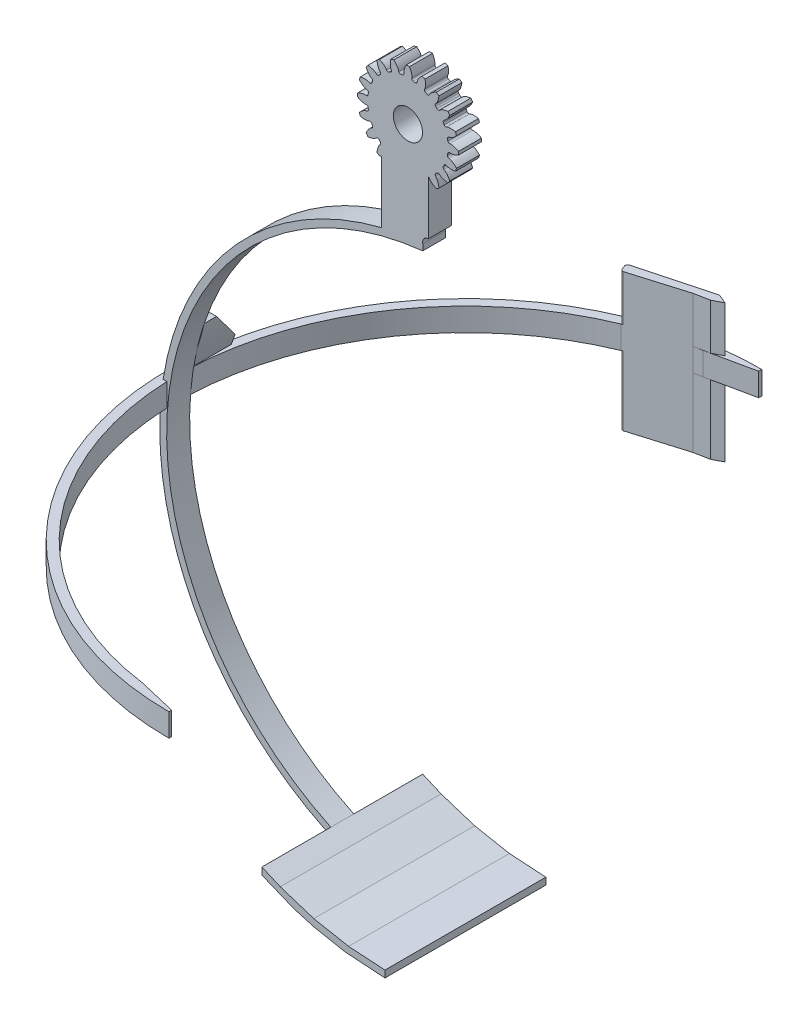
SolidWorks part; units mm, degrees
ref_plane "前视基准面" through (0, 0, 0) normal (0, 0, 1) x (1, 0, 0)
ref_plane "上视基准面" through (0, 0, 0) normal (0, 1, 0) x (1, 0, 0)
ref_plane "右视基准面" through (0, 0, 0) normal (1, 0, 0) x (0, 0, -1)
other "Configuration Table"
ref_axis "Axis1" through (0, 0, -88.99) along (0, 0, 1)
sketch "草图1" plane through (0, 0, 0) normal (0, 0, 1) x (1, 0, 0)
  circle A0 centre (0, 0) radius 22
extrude "LaShenA" add sketch "草图1" along normal blind 10
sketch "SketchA" plane through (0, 0, 10) normal (0, 0, 1) x (1, 0, 0)
  line L0 (0, 0) -> (0, 22) construction
  circle A4 centre (0, 0) radius 18.7939 construction
  circle A5 centre (0, 0) radius 22 construction
  circle A6 centre (0, 0) radius 17.5 construction
  circle A7 centre (0, 0) radius 20 construction
  arc A8 (7.1036, 21.9249) -> (0.0193, 23.0469) centre (0, 0) ccw
  arc A9 (3.9948, 17.8031) -> (3.1175, 17.2201) centre (3.2529, 17.9679) cw
  arc A10 (3.1175, 17.2201) -> (2.3563, 17.3406) centre (0, 0) ccw
  arc A11 (2.3563, 17.3406) -> (1.7022, 18.1662) centre (2.4587, 18.0937) cw
  spline S2 degree 3 poles (3.9948, 17.8031) (4.0347, 17.9825) (4.0765, 18.2192) (4.1572, 18.474) (4.1991, 18.5804) (4.2344, 18.6643) (4.2779, 18.76) (4.33, 18.867) (4.3916, 18.985) (4.4632, 19.1135) (4.5453, 19.252) (4.6387, 19.4001) (4.7439, 19.5573) (4.8615, 19.723) (4.9919, 19.8965) (5.1357, 20.0775) (5.2935, 20.2651) (5.4655, 20.4589) (5.6524, 20.6581) (5.8546, 20.8621) (6.0723, 21.0702) (6.306, 21.2817) (6.6465, 21.5732) (6.9163, 21.7854) (7.1036, 21.9249) knots 0.125068 0.125068 0.125068 0.125068 0.215847 0.244833 0.257593 0.272674 0.290074 0.309794 0.331834 0.356194 0.382875 0.411875 0.443195 0.476835 0.512796 0.551076 0.591676 0.634597 0.679837 0.727398 0.777278 0.829478 0.883999 1 1 1 1
  spline S3 degree 3 poles (1.7022, 18.1662) (1.7197, 18.3492) (1.753, 18.5872) (1.755, 18.8544) (1.7481, 18.9686) (1.7404, 19.0593) (1.7286, 19.1637) (1.7121, 19.2816) (1.69, 19.4129) (1.6617, 19.5572) (1.6263, 19.7144) (1.5833, 19.8841) (1.5318, 20.0661) (1.4712, 20.2599) (1.4008, 20.4653) (1.3199, 20.6818) (1.2279, 20.9091) (1.1241, 21.1465) (1.0079, 21.3937) (0.8787, 21.6502) (0.736, 21.9154) (0.579, 22.1887) (0.3453, 22.5712) (0.1542, 22.8564) (0.0193, 23.0469) knots 0.125068 0.125068 0.125068 0.125068 0.215847 0.244833 0.257593 0.272674 0.290074 0.309794 0.331834 0.356194 0.382875 0.411875 0.443195 0.476835 0.512796 0.551076 0.591676 0.634597 0.679837 0.727398 0.777278 0.829478 0.883999 1 1 1 1
  point P113 (0, 0)
  dimension "Db" = 37.5877
  dimension "Da" = 44
  dimension "Df" = 35
  dimension "Dn" = 40
  dimension "D2" = 2
extrude "Cut-ExtrudeA" cut sketch "SketchA" against normal blind 10
pattern_circular "www.KYTool.cn" count 20 over 360 about axis through (0, 0, -88.99) along (0, 0, 1) of "Cut-ExtrudeA"
ref_plane "基准面1" through (0, 0, 10) normal (0, 0, 1) x (1, 0, 0)
sketch "草图3" plane through (0, 0, 10) normal (0, 0, 1) x (1, 0, 0)
  circle A0 centre (0, 0) radius 6.35
  dimension "D1" = 12.7
extrude "切除-拉伸1" cut sketch "草图3" against normal up to next
sketch "草图4" plane through (0, 0, 10) normal (0, 0, 1) x (1, 0, 0)
  line L0 (0, 0) -> (0, -23.6908) construction
  line L1 (0, 0) -> (34.9845, 0) construction
  line L2 (20, 9.2558) -> (20, -13.0135) construction
  line L7 (20, -40.8194) -> (20, -43.8194)
  line L8 (20, -293.8194) -> (20, -296.8194)
  line L9 (20, -168.8194) -> (20, -43.8194)
  line L10 (20, -168.8194) -> (0, 0) construction
  line L13 (-11.473, -14.7491) -> (-11.473, -44.7491)
  line L14 (8.8831, -41.3031) -> (8.8831, -14.7491)
  line L15 (8.8831, -14.7491) -> (-11.473, -14.7491)
  arc A0 (20, -43.8194) -> (20, -293.8194) centre (20, -168.8194) ccw
  arc A3 (20, -40.8194) -> (8.8831, -41.3031) centre (20, -168.8194) ccw
  arc A4 (-11.473, -44.7491) -> (20, -296.8194) centre (20, -168.8194) ccw
  dimension "D2" = 250
  dimension "D3" = 256
  dimension "D1" = 20
  dimension "D4" = 170
  dimension "D5" = 30
  dimension "D6" = 20.3561
  dimension "D7" = 11.473
extrude "凸台-拉伸7" add sketch "草图4" against normal blind 10 contours L13 A4 L8 A0 L7 A3 L14 L15 region at (16.9025, -42.3194, 10)
sketch "草图5" plane through (0, 0, 10) normal (0, 0, 1) x (1, 0, 0)
  line L0 (-105, -154.4791) -> (20, -154.4791) construction
  line L1 (-107.361, -153.4791) -> (-107.361, -155.4791)
  line L2 (-107.361, -155.4791) -> (-105.8398, -155.4791)
  line L3 (-105.8398, -155.4791) -> (-105.8398, -153.4791)
  line L4 (-105.8398, -153.4791) -> (-107.361, -153.4791)
  dimension "D1" = 1
extrude "凸台-拉伸8" add sketch "草图5" along normal blind 1
ref_plane "基准面2" through (0, -154.4791, 0) normal (0, -1, 0) x (-1, 0, 0)
sketch "草图6" plane through (0, -154.4791, 0) normal (0, -1, 0) x (-1, 0, 0)
  line L0 (-20, -4.2865) -> (-20, 34.8821) construction
  line L1 (108, -5) -> (-41.683, -5) construction
  line L4 (-20, 124) -> (-20, 120)
  line L5 (-20, -130) -> (-20, -134)
  arc A1 (-20, -130) -> (-20, 120) centre (-20, -5) ccw
  arc A2 (-20, -134) -> (-20, 124) centre (-20, -5) ccw
  dimension "D1" = 250
  dimension "D2" = 258
extrude "凸台-拉伸9" add sketch "草图6" along normal blind 5 and the other way blind 5
sketch "草图7" plane through (0, -154.4791, 0) normal (0, -1, 0) x (-1, 0, 0)
  line L0 (-1.8665, -128.5231) -> (-20, -132.8264)
  line L2 (-20, -130) -> (-20, -134) construction
  line L3 (-20, -132.8264) -> (-20, -128.9322)
  line L4 (-20, -128.9322) -> (-1.8665, -128.5231)
extrude "切除-拉伸2" cut sketch "草图7" against normal up to next and the other way up to next contours L4 L3 L0 region at (13.9555, -154.4791, 130.0939)
sketch "草图8" plane through (0, -154.4791, 0) normal (0, -1, 0) x (-1, 0, 0)
  line L0 (-20, 122.6613) -> (0, 118.3896)
  line L1 (-20, 124) -> (-20, 120) construction
  line L2 (-20, 122.6613) -> (-20, 116.0502)
  line L3 (-20, 116.0502) -> (0, 118.3896)
  arc A0 (104.9, 0) -> (-20, 120) centre (-20, -5) ccw construction
extrude "切除-拉伸3" cut sketch "草图8" against normal up to next and the other way up to next
sketch "草图9" plane through (0, 0, 10) normal (0, 0, 1) x (1, 0, 0)
  line L0 (-4.2763, -291.4394) -> (20, -281.4909)
  line L1 (20, -293.8194) -> (20, -296.8194) construction
  line L2 (20, -281.4909) -> (20, -278.1298)
  line L3 (20, -278.1298) -> (-4.2763, -291.4394)
  arc A0 (20, -43.8194) -> (20, -293.8194) centre (20, -168.8194) ccw construction
sketch "草图10" plane through (0, -159.4791, 0) normal (0, -1, 0) x (1, 0, 0)
  line L0 (-3.6833, -117.7359) -> (2.7641, -118.98)
  line L1 (0, -118.3896) -> (20, -122.6613) construction
  line L2 (2.7641, -118.98) -> (6.8079, -121.1064)
  line L3 (6.8079, -121.1064) -> (2.7641, -122.8434)
  line L4 (2.7641, -122.8434) -> (-29.3266, -114.1968)
  line L5 (-29.3266, -114.1968) -> (-27.7971, -110.5008)
  line L6 (-27.7971, -110.5008) -> (-3.6833, -117.7359)
  arc A0 (-104.9, 0) -> (0, -118.3896) centre (20, 5) ccw construction
  arc A1 (20, 134) -> (20, -124) centre (20, 5) ccw construction
extrude "凸台-拉伸10" add sketch "草图10" along normal blind 30 and the other way blind 30
fillet "圆角1" radius 1 2 edges at (-29.3266, -139.4791, -114.1968) (-29.3266, -174.4791, -114.1968)
fillet "圆角2" radius 1 2 edges at (-27.7971, -139.4791, -110.5008) (-27.7971, -174.4791, -110.5008)
ref_plane "基准面3" through (0, -149.4791, 0) normal (0, 1, 0) x (1, 0, 0)
sketch "草图12" plane through (0, -149.4791, 0) normal (0, 1, 0) x (1, 0, 0)
  line L0 (-106.9331, 18) -> (-106.5304, 0)
  line L1 (-106.5304, 0) -> (-90.0177, 0)
  line L2 (-11.473, 0) -> (-106.5304, 0) construction
  line L3 (-90.0177, 0) -> (-90.0177, 18)
  line L4 (-90.0177, 18) -> (-106.9331, 18)
  arc A0 (-29.3266, 114.1968) -> (20, -134) centre (20, -5) ccw construction
  dimension "D1" = 18
extrude "凸台-拉伸11" add sketch "草图12" along normal blind 20
ref_plane "基准面4" through (0, 0, -18) normal (0, 0, -1) x (-1, 0, 0)
ref_plane "基准面5" through (0, 0, 0) normal (0, 0, 1) x (1, 0, 0)
sketch "草图13" plane through (0, 0, 0) normal (0, 0, 1) x (1, 0, 0)
  line L0 (-106.5304, -149.4791) -> (-104.9, -149.4791) construction
  line L1 (-106.5304, -129.4791) -> (-106.5304, -149.4791) construction
  line L2 (-106.5304, -129.4791) -> (-101.8045, -129.4791)
  line L4 (-106.5304, -129.4791) -> (-106.5304, -149.4791)
  line L5 (-98.648, -129.4791) -> (-90.0177, -129.4791)
  line L6 (-98.648, -129.4791) -> (-90.0177, -129.4791) construction
  line L7 (-90.0177, -129.4791) -> (-90.0177, -149.4791)
  line L8 (-90.0177, -149.4791) -> (-104.8955, -149.4791)
  line L9 (20, -149.4791) -> (-109, -149.4791) construction
  line L10 (-103.4948, -149.4791) -> (-90.0177, -149.4791) construction
  arc A1 (-11.473, -44.7491) -> (-106.5304, -149.4791) centre (20, -168.8194) ccw construction
  arc A3 (-98.648, -129.4791) -> (-103.4948, -149.4791) centre (20, -168.8194) ccw construction
  spline S0 degree 3 poles (-101.8045, -129.4791) (-103.9119, -136.0022) (-105.4948, -142.7024) (-106.5304, -149.4791) knots 0 0 0 0 1 1 1 1
  spline S1 degree 2 poles (-98.648, -129.4791) (-101.1177, -139.686) (-104.8955, -149.4791) knots 0 0 0 1 1 1
extrude "切除-拉伸5" cut sketch "草图13" against normal blind 20
ref_plane "基准面6" through (-109, 0, 0) normal (-1, 0, 0) x (0, 0, 1)
sketch "草图14" plane through (-109, 0, 0) normal (-1, 0, 0) x (0, 0, 1)
  line L0 (-5.3466, -129.4791) -> (-18, -144.9052)
  line L1 (-18, -129.4791) -> (0, -129.4791) construction
  line L2 (-18, -129.4791) -> (-18, -149.4791) construction
  line L3 (-18, -144.9052) -> (-18, -129.4791)
  line L4 (-18, -129.4791) -> (-5.3466, -129.4791)
extrude "切除-拉伸6" cut sketch "草图14" against normal blind 20
ref_plane "基准面7" through (0, 0, 10) normal (0, 0, 1) x (1, 0, 0)
ref_plane "基准面9" through (25, 0, 0) normal (1, 0, 0) x (0, 0, -1)
sketch "草图16" plane through (0, 0, 10) normal (0, 0, 1) x (1, 0, 0)
  line L0 (-33.5598, -281.7634) -> (-33.5598, -284.812)
  line L1 (-33.5598, -284.812) -> (-19.5663, -290.5507)
  line L2 (-19.5663, -290.5507) -> (-10.7341, -293.0749)
  line L3 (-10.7341, -293.0749) -> (2.7998, -295.6585)
  line L4 (2.7998, -295.6585) -> (20, -296.8194)
  line L5 (20, -296.8194) -> (20, -293.8194)
  line L6 (20, -293.8194) -> (4.1573, -292.8114)
  line L7 (4.1573, -292.8114) -> (-10.9473, -289.9279)
  line L8 (-10.9473, -289.9279) -> (-25.5548, -285.2229)
  line L9 (-25.5548, -285.2229) -> (-33.5598, -281.7634)
  arc A0 (20, -43.8194) -> (20, -293.8194) centre (20, -168.8194) ccw construction
  arc A1 (-107.6588, -159.4791) -> (20, -296.8194) centre (20, -168.8194) ccw construction
extrude "凸台-拉伸12" add sketch "草图16" along normal blind 30 and the other way blind 40
sketch "草图17" plane through (0, 0, 10) normal (0, 0, 1) x (1, 0, 0)
  circle A0 centre (8.8831, -41.3031) radius 2.5
  dimension "D1" = 5
extrude "切除-拉伸7" cut sketch "草图17" against normal blind 30
sketch "草图18" plane through (0, 0, 10) normal (0, 0, 1) x (1, 0, 0)
  line L1 (12.6598, -36.4705) -> (31.4752, -36.4705)
  line L2 (12.6598, -36.4705) -> (12.6598, -50.0693)
  line L3 (12.6598, -50.0693) -> (31.4752, -50.0693)
  line L4 (31.4752, -36.4705) -> (31.4752, -50.0693)
extrude "切除-拉伸8" cut sketch "草图18" against normal blind 30
sketch "草图19" plane through (0, 0, 10) normal (0, 0, 1) x (1, 0, 0)
  line L1 (6.4542, -40.7109) -> (17.0684, -40.7109)
  line L2 (6.4542, -40.7109) -> (6.4542, -46.1573)
  line L3 (6.4542, -46.1573) -> (17.0684, -46.1573)
  line L4 (17.0684, -40.7109) -> (17.0684, -46.1573)
  arc A0 (8.8831, -38.8031) -> (11.3756, -41.1103) centre (8.8831, -41.3031) ccw construction
extrude "切除-拉伸9" cut sketch "草图19" against normal blind 30
sketch "草图20" plane through (0, 0, 10) normal (0, 0, 1) x (1, 0, 0)
  line L0 (0, 16.8807) -> (0, -15.0787) construction
sketch "草图21" plane through (-106.4772, 0, 2.3816) normal (-0.9997, 0, 0.0224) x (0.0224, 0, 0.9997)
  line L0 (-21.9313, -128.301) -> (-20.3867, -149.4791)
  line L1 (-20.3867, -149.4791) -> (-2.3822, -149.4791)
  line L2 (-2.3822, -149.4791) -> (-2.253, -126.3571)
  line L3 (-2.253, -126.3571) -> (-21.9313, -128.301)
  ellipse E0 centre (0.4472, -168.8194) end of major axis (0.4472, -296.8194) minor radius 2.8623 (-0.2566, -44.7491) -> (-2.2765, -129.4791) ccw construction
extrude "切除-拉伸10" cut sketch "草图21" against normal blind 0.1
